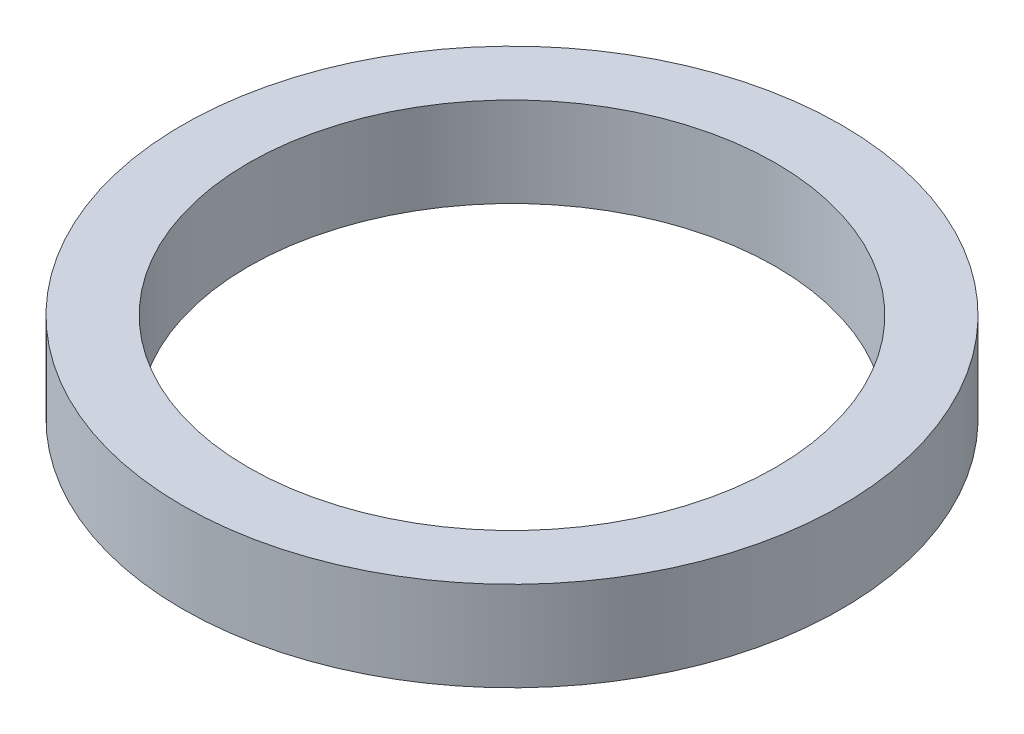
SolidWorks part; units mm, degrees
ref_plane "Front Plane" through (0, 0, 0) normal (0, 0, 1) x (1, 0, 0)
ref_plane "Top Plane" through (0, 0, 0) normal (0, 1, 0) x (1, 0, 0)
ref_plane "Right Plane" through (0, 0, 0) normal (1, 0, 0) x (0, 0, -1)
sketch "Sketch1" plane through (0, 0, 0) normal (0, 1, 0) x (1, 0, 0)
  circle A0 centre (0, 0) radius 62.5
  dimension "FLANGE_OD" = 125
extrude "Boss-Extrude1" add sketch "Sketch1" along normal blind 17
sketch "Sketch2" plane through (0, 0, 0) normal (0, 1, 0) x (1, 0, 0)
  circle A0 centre (0, 0) radius 50
  dimension "BORE_D" = 100
extrude "Cut-Extrude1" cut sketch "Sketch2" along normal through all
sketch "Sketch3" plane through (0, 17, 0) normal (0, 1, 0) x (1, 0, 0)
  circle A0 centre (0, 0) radius 26.4604 construction
  circle A1 centre (-26.4604, 0) radius 1.8259
  dimension "BOLT_D" = 3.6518
  dimension "BOLT_PCD" = 52.9208
extrude "Cut-Extrude2" cut sketch "Sketch3" against normal blind 11.858 rebuild error yes
pattern_circular "CirPattern1" count 6 over 360 rebuild error yes
